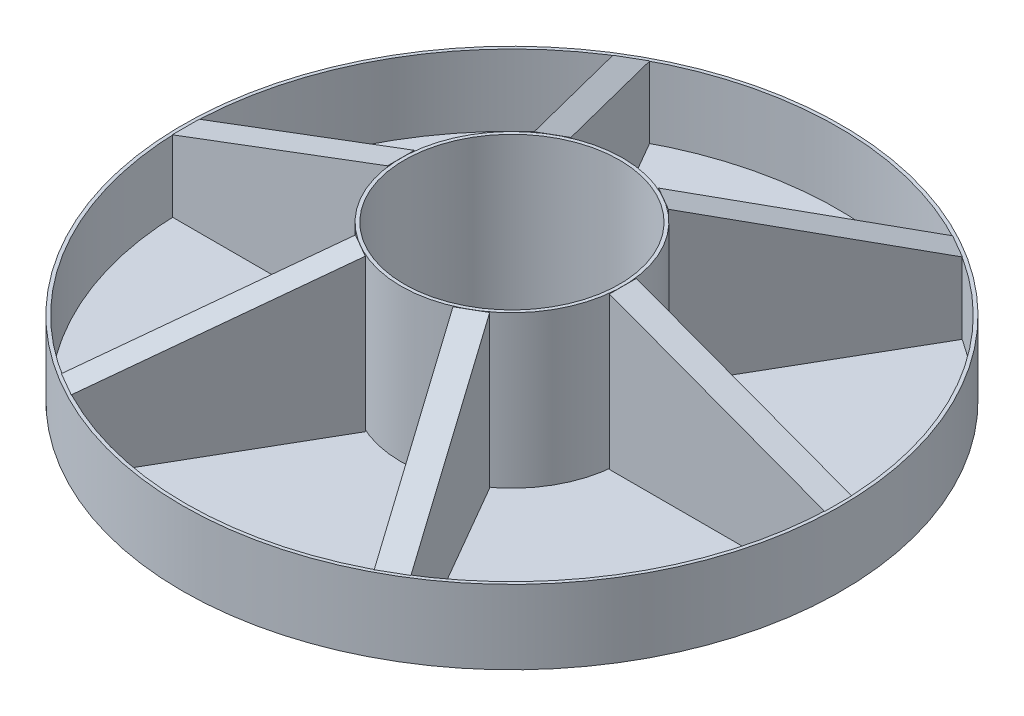
SolidWorks part; units mm, degrees
ref_plane "Front Plane" through (0, 0, 0) normal (0, 0, 1) x (1, 0, 0)
ref_plane "Top Plane" through (0, 0, 0) normal (0, 1, 0) x (1, 0, 0)
ref_plane "Right Plane" through (0, 0, 0) normal (1, 0, 0) x (0, 0, -1)
sketch "Sketch1" plane through (0, 0, 0) normal (0, 1, 0) x (1, 0, 0)
  circle A0 centre (0, 0) radius 4
  circle A1 centre (0, 0) radius 12.25
  circle A2 centre (0, 0) radius 12.125
  circle A3 centre (0, 0) radius 4.125
  dimension "D1" = 24.5
  dimension "D2" = 8
  dimension "D3" = 24.25
  dimension "D4" = 8.25
extrude "Boss-Extrude1" add sketch "Sketch1" along normal blind 5.75 contours A3 A0 region at (-4.0083, 0, 0)
extrude "Boss-Extrude2" add sketch "Sketch1<4>" along normal blind 2.75 separate body contours A1 | A2
sketch "Sketch1<4>" plane through (0, 0, 0) normal (0, 1, 0) x (1, 0, 0) same geometry as "Sketch1"
extrude "Boss-Extrude3" add sketch "Sketch1<5>" along normal blind 0.1 contours A2 A3 region at (-11.7821, 0, 0)
sketch "Sketch1<5>" plane through (0, 0, 0) normal (0, 1, 0) x (1, 0, 0) same geometry as "Sketch1"
sketch "Sketch7" plane through (0, 0, 0) normal (0, 0, 1) x (1, 0, 0)
  line L0 (-4.125, 5.75) -> (-12.125, 2.75)
  line L1 (4.125, 5.75) -> (-4.125, 5.75) construction
  line L2 (12.125, 2.75) -> (-12.125, 2.75) construction
  line L3 (-4.125, 0.1) -> (-12.125, 0.1)
  line L4 (12.125, 0.1) -> (-12.125, 0.1) construction
  line L5 (4.125, 0.1) -> (-4.125, 0.1) construction
  line L6 (-12.125, 0.1) -> (-12.125, 2.75)
  line L7 (-12.125, 2.75) -> (-12.125, 0.1)
  line L8 (-4.125, 0.1) -> (-4.125, 5.75)
extrude "Boss-Extrude5" add sketch "Sketch7" along normal mid plane 1 separate body contours L3 L8 L0 L6 region at (-7.6431, 2.2654, 0)
pattern_circular "CirPattern4" count 6 over 360 about axis through (0, 5.75, 0) along (0, 1, 0) of bodies 104
